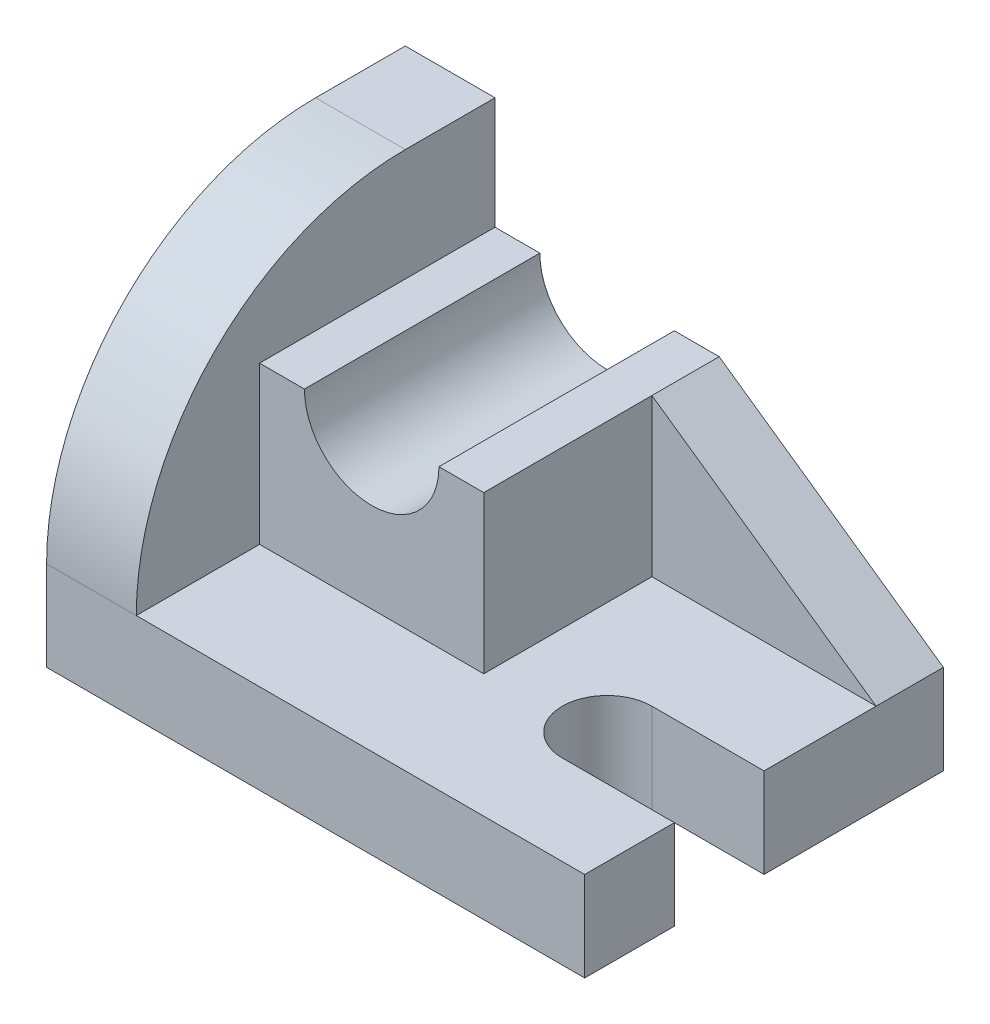
SolidWorks part; units mm, degrees
ref_plane "Front Plane" through (0, 0, 0) normal (0, 0, 1) x (1, 0, 0)
ref_plane "Top Plane" through (0, 0, 0) normal (0, 1, 0) x (1, 0, 0)
ref_plane "Right Plane" through (0, 0, 0) normal (1, 0, 0) x (0, 0, -1)
sketch "Sketch2" plane through (0, 0, 0) normal (0, 0, 1) x (1, 0, 0)
  line L0 (-20, 0) -> (20, 0)
  line L1 (20, 0) -> (20, 28)
  line L2 (20, 28) -> (12, 28)
  line L3 (-20, 28) -> (-20, 0)
  line L4 (20, 0) -> (60, 0)
  line L5 (60, 0) -> (20, 28)
  line L6 (-20, 0) -> (-36, 0)
  line L7 (-36, 0) -> (-36, 48)
  line L8 (-36, 48) -> (-20, 48)
  line L9 (-20, 48) -> (-20, 0)
  line L10 (60, 0) -> (60, -16)
  line L11 (60, -16) -> (-36, -16)
  line L12 (-36, -16) -> (-36, 0)
  line L13 (60, 0) -> (-36, 0)
  line L14 (-12, 28) -> (-20, 28)
  arc A0 (12, 28) -> (-12, 28) centre (0, 28) cw
  point P4 (0, 0)
  dimension "D1" = 40
  dimension "D2" = 16
  dimension "D3" = 24
  dimension "D4" = 40
  dimension "D5" = 16
  dimension "D6" = 48
  dimension "D7" = 28
extrude "Boss-Extrude1" add sketch "Sketch2" along normal blind 42 contours L2 A0 L14 L3 L0 L1 region at (0, 11.7459, 0)
extrude "Boss-Extrude2" add sketch "Sketch2<3>" along normal blind 64 contours L12 L11 L10 L4 L0 L6 region at (12, -8, 0)
sketch "Sketch2<3>" plane through (0, 0, 0) normal (0, 0, 1) x (1, 0, 0) same geometry as "Sketch2"
extrude "Boss-Extrude3" add sketch "Sketch2<4>" along normal blind 12 contours L4 L5 L1 region at (33.3333, 9.3333, 0)
sketch "Sketch2<4>" plane through (0, 0, 0) normal (0, 0, 1) x (1, 0, 0) same geometry as "Sketch2"
extrude "Boss-Extrude4" add sketch "Sketch2<5>" along normal blind 16 contours L9 L8 L7 L6 L3 region at (-28, 24, 0)
sketch "Sketch2<5>" plane through (0, 0, 0) normal (0, 0, 1) x (1, 0, 0) same geometry as "Sketch2"
sketch "Sketch3" plane through (0, 0, 0) normal (1, 0, 0) x (0, 0, -1)
  line L0 (-64, 0) -> (-12, 0) construction
  line L1 (-64, 0) -> (-64, -16) construction
  line L2 (-64, 0) -> (-16, 0)
  line L3 (-16, 0) -> (-16, 48)
  arc A0 (-16, 48) -> (-64, 0) centre (-16, 0) ccw
extrude "Boss-Extrude5" add sketch "Sketch3" against normal blind 16 from offset 20 offset against normal yes
sketch "Sketch4" plane through (0, 0, 0) normal (0, 1, 0) x (1, 0, 0)
  line L0 (60, -32) -> (40, -32)
  line L1 (60, -64) -> (60, -12) construction
  line L2 (40, -32) -> (40, -48)
  line L3 (40, -48) -> (60, -48)
  line L4 (-20, -64) -> (60, -64) construction
  line L5 (60, -32) -> (60, -48)
  arc A0 (40, -32) -> (40, -48) centre (40, -40) ccw
  dimension "D1" = 16
  dimension "D2" = 20
  dimension "D3" = 16
extrude "Cut-Extrude1" cut sketch "Sketch4" against normal through all both and the other way through all contours L2 A0 | L5 L0 L2 L3 region at (50, 0, 40) region at (36.6047, 0, 40)
